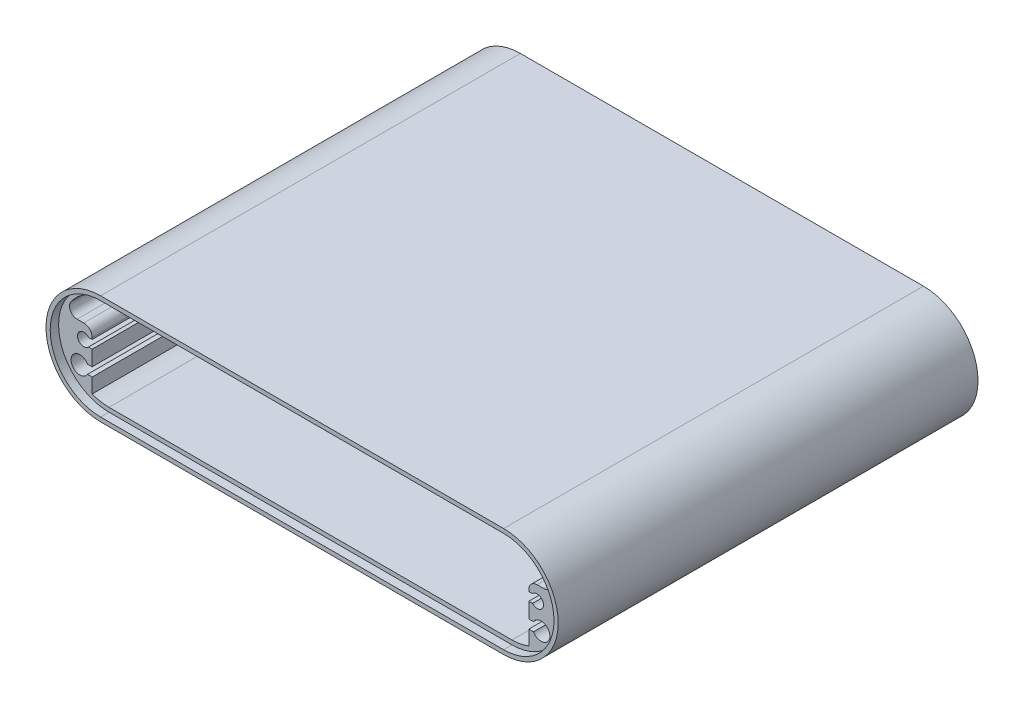
SolidWorks part; units mm, degrees
ref_plane "Front Plane" through (0, 0, 0) normal (0, 0, 1) x (1, 0, 0)
ref_plane "Top Plane" through (0, 0, 0) normal (0, 1, 0) x (1, 0, 0)
ref_plane "Right Plane" through (0, 0, 0) normal (1, 0, 0) x (0, 0, -1)
sketch "Sketch1" plane through (0, 0, 0) normal (0, 0, 1) x (1, 0, 0)
  line L0 (0, 0) -> (0, 16.0369) construction
  line L1 (30.5, 0) -> (-30.5, 0) construction
  line L2 (24, 6.5) -> (-24, 6.5)
  line L3 (24, -6.5) -> (-24, -6.5)
  line L4 (0, 0) -> (0, -11.8688) construction
  line L5 (24, 5.5) -> (-24, 5.5)
  line L6 (-24, -5.5) -> (24, -5.5)
  line L7 (27, 1.7) -> (27.7947, 1.7)
  line L8 (26, 0.5) -> (26, 0.7)
  line L9 (-26, -0.5) -> (-26.441, -0.5)
  line L10 (-26.441, 0.5) -> (-26, 0.5)
  line L11 (-26, -5.1235) -> (-26, -3.375)
  line L12 (-26, -3.375) -> (-26.5557, -3.375)
  line L13 (-26.5557, -2.325) -> (-26, -2.325)
  line L14 (-26, -2.325) -> (-26, -0.5)
  line L15 (-26, 0.5) -> (-26, 0.7)
  line L16 (-27, 1.7) -> (-27.7947, 1.7)
  line L17 (26, -2.325) -> (26, -0.5)
  line L18 (26.5557, -2.325) -> (26, -2.325)
  line L19 (26, -3.375) -> (26.5557, -3.375)
  line L20 (26, -5.1235) -> (26, -3.375)
  line L21 (26.441, 0.5) -> (26, 0.5)
  line L22 (26, -0.5) -> (26.441, -0.5)
  arc A0 (-24, 6.5) -> (-24, -6.5) centre (-24, 0) ccw
  arc A1 (-24, 5.5) -> (-28.5372, 3.1087) centre (-24, 0) ccw
  arc A2 (-26.5557, -2.325) -> (-26.5557, -3.375) centre (-27.465, -2.85) ccw
  arc A3 (-26.441, 0.5) -> (-26.441, -0.5) centre (-27, 0) ccw
  arc A4 (-27, 1.7) -> (-26, 0.7) centre (-27, 0.7) cw
  arc A5 (-26, -5.1235) -> (-24, -5.5) centre (-24, 0) ccw
  arc A6 (-27.7947, 1.7) -> (-28.5372, 3.1087) centre (-27.7947, 2.6) cw
  arc A7 (27.7947, 1.7) -> (28.5372, 3.1087) centre (27.7947, 2.6) ccw
  arc A8 (26, -5.1235) -> (24, -5.5) centre (24, 0) cw
  arc A9 (27, 1.7) -> (26, 0.7) centre (27, 0.7) ccw
  arc A10 (26.441, 0.5) -> (26.441, -0.5) centre (27, 0) cw
  arc A11 (26.5557, -2.325) -> (26.5557, -3.375) centre (27.465, -2.85) cw
  arc A12 (24, 5.5) -> (28.5372, 3.1087) centre (24, 0) cw
  arc A13 (24, 6.5) -> (24, -6.5) centre (24, 0) cw
  point P6 (0, 6.5)
  point P10 (0, -6.5)
  point P15 (0, 5.5)
  point P23 (-30.5, 0)
  point P56 (0, -5.5)
  dimension "D2" = 6.5
  dimension "D4" = 5.5
  dimension "D5" = 2.1
  dimension "D6" = 1.5
  dimension "D7" = 27
  dimension "D8" = 30.5
  dimension "D16" = 1
  dimension "D17" = 0.9
  dimension "D19" = 1.7
  dimension "D1" = 13
  dimension "D3" = 1
  dimension "D9" = 27.465
  dimension "D10" = 1
  dimension "D11" = 0.5
  dimension "D12" = 26
  dimension "D13" = 1.05
  dimension "D14" = 0.525
  dimension "D15" = 3.65
  dimension "D20" = 1
extrude "Boss-Extrude1" add sketch "Sketch1" along normal blind 25 and the other way blind 25
sketch "Sketch2" plane through (0, 0, 25) normal (0, 0, 1) x (1, 0, 0)
  line L0 (24, 6.5) -> (-24, 6.5) construction
  line L1 (-24, -6.5) -> (24, -6.5) construction
  line L2 (24, 6.5) -> (-24, 6.5) construction
  line L3 (-24, -6.5) -> (24, -6.5) construction
  line L4 (24, 6) -> (-24, 6)
  line L5 (-24, -6) -> (24, -6)
  arc A0 (-24, 6.5) -> (-24, -6.5) centre (-24, 0) ccw construction
  arc A1 (24, -6.5) -> (24, 6.5) centre (24, 0) ccw construction
  arc A2 (-24, 6.5) -> (-24, -6.5) centre (-24, 0) ccw construction
  arc A3 (24, -6.5) -> (24, 6.5) centre (24, 0) ccw construction
  arc A4 (-24, 6) -> (-24, -6) centre (-24, 0) ccw
  arc A5 (24, -6) -> (24, 6) centre (24, 0) ccw
  dimension "D1" = 0.5
extrude "Cut-Extrude1" cut sketch "Sketch2" against normal blind 1
mirror "Mirror1" about plane through (0, 0, 0) normal (0, 0, 1) of "Cut-Extrude1"
